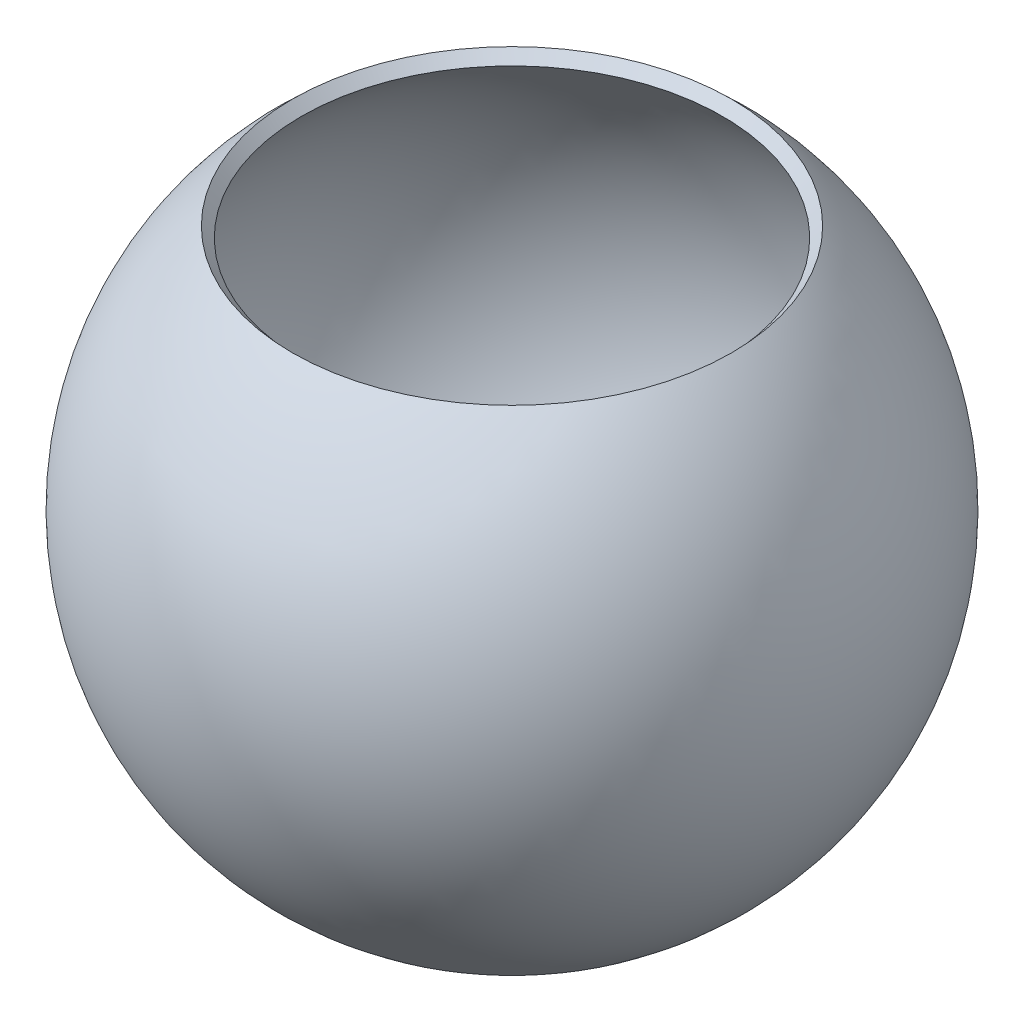
SolidWorks part; units mm, degrees
ref_plane "Front Plane" through (0, 0, 0) normal (0, 0, 1) x (1, 0, 0)
ref_plane "Top Plane" through (0, 0, 0) normal (0, 1, 0) x (1, 0, 0)
ref_plane "Right Plane" through (0, 0, 0) normal (1, 0, 0) x (0, 0, -1)
sketch "Sketch1" plane through (0, 0, 0) normal (0, 0, 1) x (1, 0, 0)
  line L3 (0, -200000) -> (0, 218797.9879) construction
  line L4 (0, -77.7363) -> (0, -84.0863)
  line L5 (101.6, 181.906) -> (97.3667, 177.1729)
  line L6 (0, 0) -> (0, -77.7363) construction
  arc A2 (0, -84.0863) -> (101.6, 181.906) centre (0, 68.3137) ccw
  arc A3 (0, -77.7363) -> (97.3667, 177.1729) centre (0, 68.3137) ccw
  arc A4 (0, -77.7363) -> (97.3667, 177.1729) centre (0, 68.3137) ccw construction
  point P0 (84.455, 153.392)
  point P10 (0, 0)
  point P11 (0, -53.4194)
  point P14 (0, -59.7694)
  point P16 (101.6, 206.2229)
  point P18 (97.3667, 201.4899)
  point P20 (0, 0)
revolve "Revolve1" add sketch "Sketch1" angle 360 about L6
